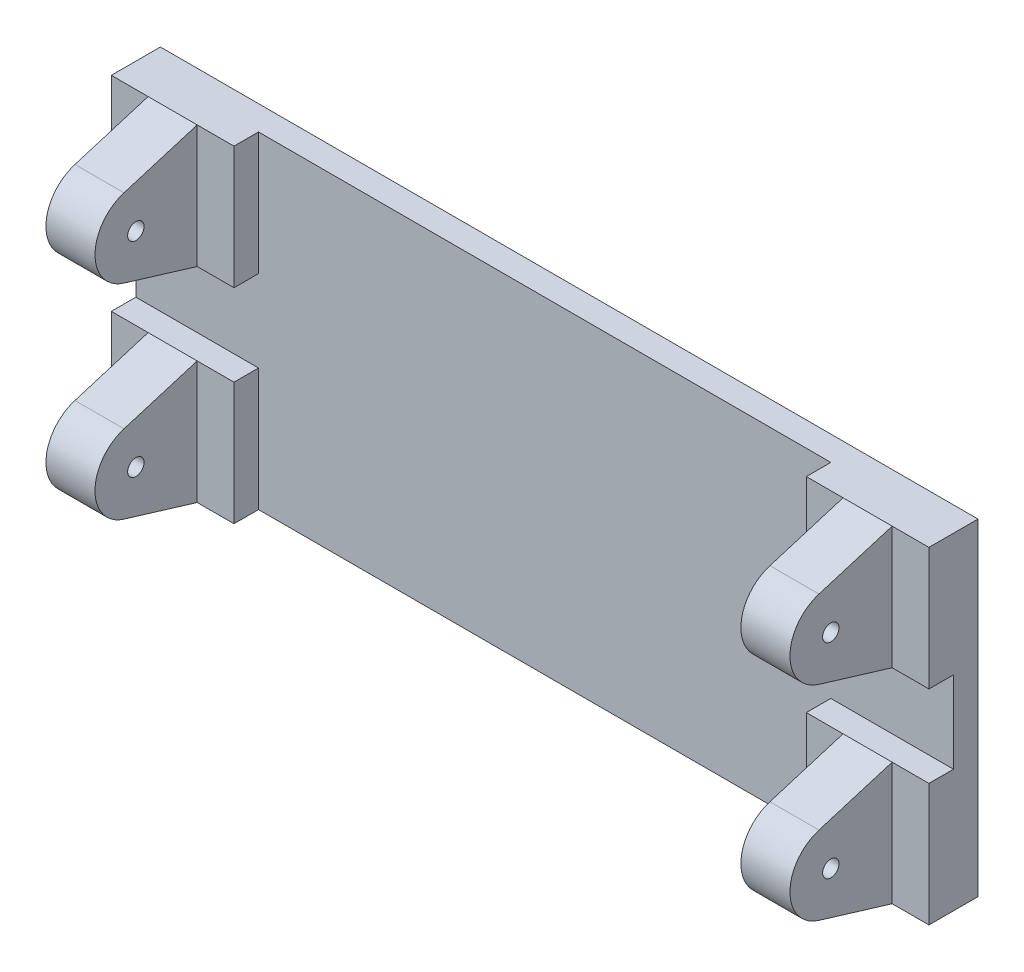
SolidWorks part; units mm, degrees
ref_plane "Front Plane" through (0, 0, 0) normal (0, 0, 1) x (1, 0, 0)
ref_plane "Top Plane" through (0, 0, 0) normal (0, 1, 0) x (1, 0, 0)
ref_plane "Right Plane" through (0, 0, 0) normal (1, 0, 0) x (0, 0, -1)
sketch "Sketch1" plane through (0, 0, 0) normal (0, 0, 1) x (1, 0, 0)
  line L1 (-50, 20) -> (50, 20)
  line L2 (-50, 20) -> (-50, -20)
  line L3 (-50, -20) -> (50, -20)
  line L4 (50, 20) -> (50, -20)
  line L5 (-50, 20) -> (50, -20) construction
  line L6 (-50, -20) -> (50, 20) construction
  point P0 (0, 0)
  dimension "D1" = 40
  dimension "D2" = 100
extrude "Boss-Extrude1" add sketch "Sketch1" along normal blind 3
sketch "Sketch2" plane through (0, 0, 3) normal (0, 0, 1) x (1, 0, 0)
  line L0 (55, 0) -> (-55, 0) construction
  line L1 (-50, 20) -> (-35, 20)
  line L2 (-50, 20) -> (-50, 5)
  line L3 (-50, 5) -> (-35, 5)
  line L4 (-35, 20) -> (-35, 5)
  line L5 (-50, -5) -> (-35, -5)
  line L6 (-35, -20) -> (-35, -5)
  line L7 (-50, -20) -> (-35, -20)
  line L8 (-50, -20) -> (-50, -5)
  line L9 (0, -55) -> (0, 55) construction
  line L10 (50, -20) -> (50, -5)
  line L11 (50, -20) -> (35, -20)
  line L12 (35, -20) -> (35, -5)
  line L13 (50, -5) -> (35, -5)
  line L14 (50, 5) -> (35, 5)
  line L15 (35, 20) -> (35, 5)
  line L16 (50, 20) -> (35, 20)
  line L17 (50, 20) -> (50, 5)
  dimension "D1" = 15
extrude "Boss-Extrude2" add sketch "Sketch2" along normal blind 3
sketch "Sketch3" plane through (-50, 0, 0) normal (-1, 0, 0) x (0, 0, 1)
  line L0 (6, 5) -> (14.9514, 7.7153)
  line L1 (6, 20) -> (14.9514, 17.2847)
  line L2 (6, 20) -> (6, 5)
  arc A0 (14.9514, 7.7153) -> (14.9514, 17.2847) centre (13.5, 12.5) ccw
  circle A1 centre (13.5, 12.5) radius 1
  point P9 (13.5, 12.7987)
  dimension "D1" = 7.5
  dimension "D2" = 10
  dimension "D3" = 2
extrude "Boss-Extrude3" add sketch "Sketch3" against normal blind 15
sketch "Sketch4" plane through (0, 20, 0) normal (0, 1, 0) x (1, 0, 0)
  line L0 (-35, -6) -> (-50, -6) construction
  line L1 (-39.5, -6) -> (-35, -6)
  line L2 (-39.5, -6) -> (-39.5, -18.5)
  line L3 (-39.5, -18.5) -> (-35, -18.5)
  line L4 (-35, -6) -> (-35, -18.5)
  line L5 (-50, -18.5) -> (-35, -18.5) construction
  line L6 (-50, -6) -> (-45.5, -6)
  line L7 (-50, -6) -> (-50, -18.5)
  line L8 (-50, -18.5) -> (-45.5, -18.5)
  line L9 (-45.5, -6) -> (-45.5, -18.5)
  line L10 (-35, -14.9514) -> (-35, -6) construction
  line L11 (-35, -12.25) -> (-39.5, -12.25) construction
  line L12 (-45.5, -12.25) -> (-50, -12.25) construction
  dimension "D1" = 6
extrude "Cut-Extrude1" cut sketch "Sketch4" against normal up to next
mirror "Mirror1" about plane through (0, 0, 0) normal (0, 1, 0) of "Cut-Extrude1", "Boss-Extrude3"
mirror "Mirror2" about plane through (0, 0, 0) normal (1, 0, 0) of "Mirror1"
